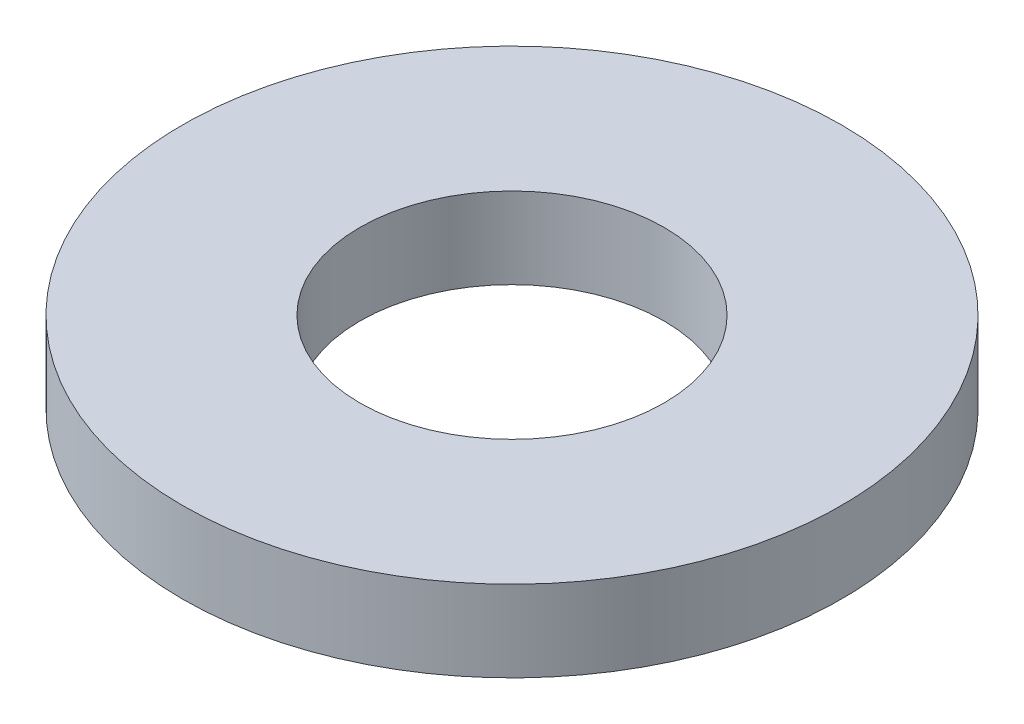
SolidWorks part; units mm, degrees
ref_plane "Front Plane" through (0, 0, 0) normal (0, 0, 1) x (1, 0, 0)
ref_plane "Top Plane" through (0, 0, 0) normal (0, 1, 0) x (1, 0, 0)
ref_plane "Right Plane" through (0, 0, 0) normal (1, 0, 0) x (0, 0, -1)
sketch "Sketch1" plane through (0, 0, 0) normal (0, 1, 0) x (1, 0, 0)
  circle A0 centre (0, 0) radius 97.5
  dimension "FLANGE_OD" = 195
extrude "Boss-Extrude1" add sketch "Sketch1" along normal blind 24
sketch "Sketch2" plane through (0, 0, 0) normal (0, 1, 0) x (1, 0, 0)
  circle A0 centre (0, 0) radius 45
  dimension "BORE_D" = 90
extrude "Cut-Extrude1" cut sketch "Sketch2" along normal through all
sketch "Sketch3" plane through (0, 24, 0) normal (0, 1, 0) x (1, 0, 0)
  circle A0 centre (0, 0) radius 33.6386 construction
  circle A1 centre (-33.6386, 0) radius 8.0882
  dimension "BOLT_D" = 16.1763
  dimension "BOLT_PCD" = 67.2772
extrude "Cut-Extrude2" cut sketch "Sketch3" against normal blind 18.1755 rebuild error yes
pattern_circular "CirPattern1" count 8 over 360 rebuild error yes
